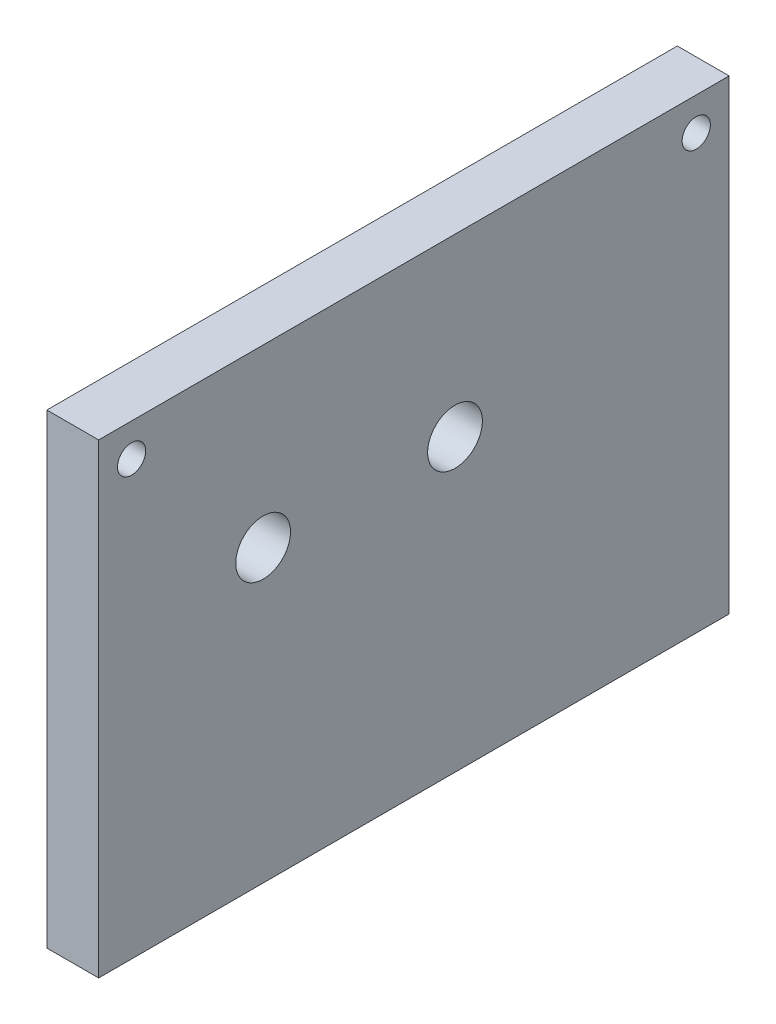
SolidWorks part; units mm, degrees
material "Acrylic (Medium-high impact)"
ref_plane "Front Plane" through (0, 0, 0) normal (0, 0, 1) x (1, 0, 0)
ref_plane "Top Plane" through (0, 0, 0) normal (0, 1, 0) x (1, 0, 0)
ref_plane "Right Plane" through (0, 0, 0) normal (1, 0, 0) x (0, 0, -1)
sketch "Sketch1" plane through (0, 0, 0) normal (1, 0, 0) x (0, 0, -1)
  line L0 (-65.405, 46.355) -> (65.405, 46.355) construction
  line L1 (-73.025, 53.975) -> (73.025, 53.975)
  line L2 (-73.025, 53.975) -> (-73.025, -53.975)
  line L3 (-73.025, -53.975) -> (73.025, -53.975)
  line L4 (73.025, 53.975) -> (73.025, -53.975)
  line L5 (-73.025, 53.975) -> (73.025, -53.975) construction
  line L6 (-73.025, -53.975) -> (73.025, 53.975) construction
  line L7 (-73.025, -50.865) -> (73.025, -50.865) construction
  line L8 (-73.025, -50.865) -> (-73.025, -62.865) construction
  line L9 (-73.025, -62.865) -> (73.025, -62.865) construction
  line L10 (73.025, -50.865) -> (73.025, -62.865) construction
  circle A2 centre (-34.925, 13.335) radius 6.3436
  circle A3 centre (-34.925, 13.335) radius 32.8422 construction
  circle A4 centre (9.525, 13.335) radius 6.3437
  circle A5 centre (9.525, 13.335) radius 32.8422 construction
  circle A6 centre (-34.925, 13.335) radius 13.7287 construction
  circle A7 centre (9.525, 13.335) radius 13.7287 construction
  point P0 (0, 0)
  point P20 (0, 46.355)
  dimension "D4" = 76.2
  dimension "D5" = 65.6844
  dimension "D8" = 27.4574
  dimension "D9" = 12.6873
  dimension "D11" = 7.62
  dimension "D1" = 146.05
  dimension "D2" = 107.95
  dimension "D3" = 12
  dimension "D6" = 67.31
  dimension "D7" = 44.45
  dimension "D10" = 63.5
  dimension "D12" = 7.62
extrude "Boss-Extrude1" add sketch "Sketch1" along normal blind 12
sketch "Sketch2" plane through (0, -53.975, 0) normal (0, -1, 0) x (1, 0, 0)
  line L0 (6, -60.325) -> (6, 60.325) construction
  line L1 (12, 73.025) -> (0, 73.025) construction
  line L2 (12, -73.025) -> (0, -73.025) construction
  point P4 (6, 0)
  point P9 (6, -73.025)
  dimension "D1" = 12.7
hole_wizard "Tap Drill for #10-32 Tap1" positions "Sketch3" profile "Sketch4" hole size "#10-32" standard "ANSI Inch"
sketch "Sketch3" plane through (0, -53.975, 0) normal (0, -1, 0) x (-1, 0, 0)
  point P0 (-6, -60.325)
  point P3 (-6, 0)
  point P6 (-6, 60.325)
sketch "Sketch4" plane through (6, -53.975, 60.325) normal (1, 0, 0) x (0, 0, -1)
  line L0 (0, 0) -> (0, 13.9133)
  line L1 (0, 13.9133) -> (2.0193, 12.7)
  line L2 (2.0193, 12.7) -> (2.0193, 0)
  line L5 (2.0193, 0) -> (0, 0)
  line L10 (0, 13.9133) -> (-2.0193, 12.7) construction
  line L11 (0, -6.35) -> (0, 107.95) construction
  dimension "Hole Dia." = 4.0386
  dimension "Hole Depth" = 12.7
  dimension "Drill Angle" = 118
hole_wizard "1/4 Clearance Hole1" positions "Sketch5" profile "Sketch6" hole size "1/4" standard "ANSI Inch"
sketch "Sketch5" plane through (0, 0, 0) normal (-1, 0, 0) x (0, 0, 1)
  point P0 (-65.405, 46.355)
  point P3 (65.405, 46.355)
sketch "Sketch6" plane through (0, 46.355, -65.405) normal (0, 1, 0) x (0, 0, 1)
  line L0 (0, 0) -> (0, 14.6611)
  line L1 (0, 14.6611) -> (3.2639, 12.7)
  line L2 (3.2639, 12.7) -> (3.2639, 0)
  line L5 (3.2639, 0) -> (0, 0)
  line L10 (0, 14.6611) -> (-3.2639, 12.7) construction
  line L11 (0, -6.35) -> (0, 107.95) construction
  dimension "Hole Dia." = 6.5278
  dimension "Hole Depth" = 12.7
  dimension "Drill Angle" = 118
